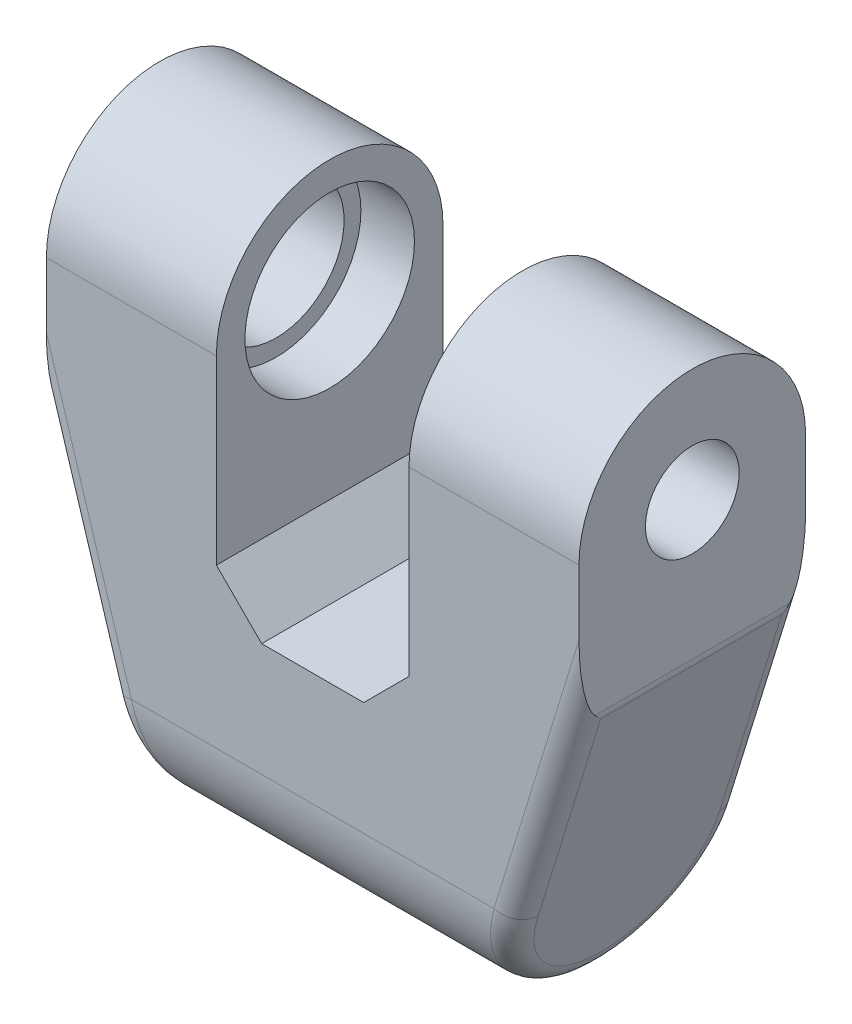
SolidWorks part; units mm, degrees
ref_plane "Front Plane" through (0, 0, 0) normal (0, 0, 1) x (1, 0, 0)
ref_plane "Top Plane" through (0, 0, 0) normal (0, 1, 0) x (1, 0, 0)
ref_plane "Right Plane" through (0, 0, 0) normal (1, 0, 0) x (0, 0, -1)
sketch "Sketch1" plane through (0, 0, 0) normal (1, 0, 0) x (0, 0, -1)
  circle A0 centre (0, 0) radius 3 construction
  circle A1 centre (0, 0) radius 9.5
  circle A2 centre (0, 0) radius 12.7
  dimension "D1" = 6
  dimension "D2" = 19
  dimension "D3" = 25.4
extrude "Boss-Extrude1" add sketch "Sketch1" along normal blind 6
sketch "Sketch2" plane through (0, 0, 0) normal (-1, 0, 0) x (0, 0, 1)
  circle A0 centre (0, 0) radius 9.5 construction
  circle A1 centre (0, 0) radius 12.7
  circle A2 centre (0, 0) radius 12.7
  circle A3 centre (0, 0) radius 9.5
  circle A4 centre (0, 0) radius 7.62
  circle M3 centre (0, 0) radius 12.7
  circle M4 centre (0, 0) radius 9.5
  dimension "D2" = 15.24
  dimension "D1" = 0
extrude "Boss-Extrude2" add sketch "Sketch2" along normal blind 13.05 contours A4 M4 | M3 M4 region at (0, 0, -12.3408) region at (0, 0, -9.2313)
ref_plane "Plane1" through (16.795, 0, 0) normal (1, 0, 0) x (0, 0, -1)
mirror "Mirror2" about plane through (16.795, 0, 0) normal (1, 0, 0) of bodies 102
sketch "Sketch3" plane through (6, 0, 0) normal (1, 0, 0) x (0, 0, -1)
  line L0 (-12.7, 0) -> (-12.7, -38.1)
  line L1 (12.7, 0) -> (12.7, -38.1)
  arc A0 (-12.7, -38.1) -> (12.7, -38.1) centre (0, -38.1) ccw
  circle A1 centre (0, 0) radius 12.7
  circle A2 centre (0, 0) radius 12.7
  point P7 (-10.4092, -37.6591)
  point P8 (10.4092, -37.6608)
  circle M2 centre (0, 0) radius 12.7
  dimension "D2" = 38.1
  dimension "D3" = 12.7
  dimension "D1" = 0
extrude "Boss-Extrude3" add sketch "Sketch3" against normal up to surface (19.05 mm away) contours L0 A0 L1 M2 region at (6, -29.0246, 0) up to face at (-13.05, 0, 7.62)
extrude "Boss-Extrude4" add sketch "Sketch3<3>" along normal up to surface (40.64 mm away) from surface contours L0 A0 L1 M2 region at (6, -29.0246, 0) up to face at (46.64, 0, 7.62) starting at face at (27.59, 0, -12.7)
sketch "Sketch3<3>" plane through (6, 0, 0) normal (1, 0, 0) x (0, 0, -1) same geometry as "Sketch3"
sketch "Sketch4" plane through (6, 0, 0) normal (1, 0, 0) x (0, 0, -1)
  line L0 (-12.7, -25.4) -> (12.7, -25.4)
  line L2 (-12.7, 0) -> (-12.7, -38.1)
  line L3 (12.7, -38.1) -> (12.7, 0)
  line L4 (-12.7, 0) -> (-12.7, -38.1)
  line L5 (12.7, -38.1) -> (12.7, 0)
  arc A2 (12.7, 0) -> (-12.7, 0) centre (0, 0) ccw
  arc A3 (-12.7, -38.1) -> (12.7, -38.1) centre (0, -38.1) ccw
  arc A4 (12.7, 0) -> (-12.7, 0) centre (0, 0) ccw
  arc A5 (-12.7, -38.1) -> (12.7, -38.1) centre (0, -38.1) ccw
  line M7 (-12.7, 0) -> (-12.7, -38.1)
  arc M8 (-12.7, -38.1) -> (12.7, -38.1) centre (0, -38.1) ccw
  line M9 (12.7, -38.1) -> (12.7, 0)
  dimension "D2" = 25.4
  dimension "D1" = 0
extrude "Boss-Extrude5" add sketch "Sketch4" along normal up to surface (21.59 mm away) contours L0 M7 M8 M9 region at (6, -36.9145, 0) up to face at (27.59, -19.05, 0)
sketch "Sketch5" plane through (0, 0, 12.7) normal (0, 0, 1) x (1, 0, 0)
  line L0 (6, -15.875) -> (-13.05, -15.875) construction
  line L2 (-13.05, -38.1) -> (-13.05, -50.8) construction
  line L8 (6, 0) -> (-13.05, 0)
  line L9 (-13.05, 0) -> (-13.05, -38.1)
  line L10 (-13.05, -38.1) -> (46.64, -38.1)
  line L11 (46.64, -38.1) -> (46.64, 0)
  line L12 (46.64, 0) -> (27.59, 0)
  line L13 (27.59, 0) -> (27.59, -25.4)
  line L14 (27.59, -25.4) -> (6, -25.4)
  line L15 (6, -25.4) -> (6, 0)
  line L16 (6, 0) -> (-13.05, 0)
  line L17 (-13.05, 0) -> (-13.05, -38.1)
  line L18 (-13.05, -38.1) -> (46.64, -38.1)
  line L19 (46.64, -38.1) -> (46.64, 0)
  line L20 (46.64, 0) -> (27.59, 0)
  line L21 (27.59, 0) -> (27.59, -25.4)
  line L22 (27.59, -25.4) -> (6, -25.4)
  line L23 (6, -25.4) -> (6, 0)
  line L25 (-13.05, -38.1) -> (-13.05, -50.8)
  line L26 (-13.05, -50.8) -> (46.64, -50.8)
  line L27 (46.64, -50.8) -> (46.64, -38.1)
  line L28 (-13.05, -15.875) -> (-2.255, -50.8)
  line L29 (46.64, -15.875) -> (35.845, -50.8)
  line L30 (-13.05, -50.8) -> (46.64, -50.8) construction
  point P16 (38.5128, -53.975)
  point P17 (0, 0)
  point P18 (43.6444, -53.975)
  point P21 (0, 0)
  point P22 (0, 0)
  line M14 (-13.05, -38.1) -> (46.64, -38.1)
  line M15 (46.64, -38.1) -> (46.64, 0)
  dimension "D2" = 15.875
  dimension "D3" = 38.1
  dimension "D1" = 0
extrude "Cut-Extrude1" cut sketch "Sketch5" against normal through all contours L28 L25 L26 M14 | L28 L17 M14 | L29 L26 L27 M14 | L29 M15 M14 region at (-10.7602, -30.6917, 12.7) region at (-8.5612, -44.9204, 12.7) region at (44.3502, -30.6917, 12.7) region at (42.1512, -44.9204, 12.7)
fillet "Fillet1" radius 2.54 8 edges at (43.2052, -26.9875, 12.7) (43.2052, -26.9875, -12.7) (-9.6152, -26.9875, -12.7) (-13.05, -15.875, 0) (-9.6152, -26.9875, 12.7) (-2.255, -50.8, 0) (35.845, -50.8, 0) (46.64, -15.875, 0)
chamfer "Chamfer1" distance 5.08 angle 45 2 edges at (27.59, -25.4, 0) (6, -25.4, 0)
sketch "Sketch6" plane through (46.64, 0, 0) normal (1, 0, 0) x (0, 0, -1)
  line L3 (-12.7, 0) -> (-12.7, -7.2738)
  line L4 (-10.9101, -15.4914) -> (10.9101, -15.4914)
  line L5 (12.7, -7.2738) -> (12.7, 0)
  line L6 (-12.7, 0) -> (-12.7, -7.2738)
  line L7 (-10.9101, -15.4914) -> (10.9101, -15.4914)
  line L8 (12.7, -7.2738) -> (12.7, 0)
  circle A0 centre (0, 0) radius 7.62 construction
  arc A1 (12.7, 0) -> (-12.7, 0) centre (0, 0) ccw
  arc A2 (12.7, 0) -> (-12.7, 0) centre (0, 0) ccw
  circle A3 centre (0, 0) radius 7.62
  circle A4 centre (0, 0) radius 5.25
  ellipse E2 centre (-10.16, -7.2738) end of major axis (-10.16, -15.875) minor radius 2.54 (-12.7, -7.2738) -> (-10.9101, -15.4914) ccw
  ellipse E3 centre (10.16, -7.2738) end of major axis (10.16, -15.875) minor radius 2.54 (10.9101, -15.4914) -> (12.7, -7.2738) ccw
  ellipse E4 centre (-10.16, -7.2738) end of major axis (-10.16, -15.875) minor radius 2.54 (-12.7, -7.2738) -> (-10.9101, -15.4914) ccw
  ellipse E5 centre (10.16, -7.2738) end of major axis (10.16, -15.875) minor radius 2.54 (10.9101, -15.4914) -> (12.7, -7.2738) ccw
  circle M14 centre (0, 0) radius 7.62
  dimension "D2" = 10.5
  dimension "D1" = 0
extrude "Boss-Extrude6" add sketch "Sketch6" against normal up to surface (13.05 mm away) contours A4 M14 region at (46.64, 0, 7.4045) up to face at (33.59, 0, 7.62)
